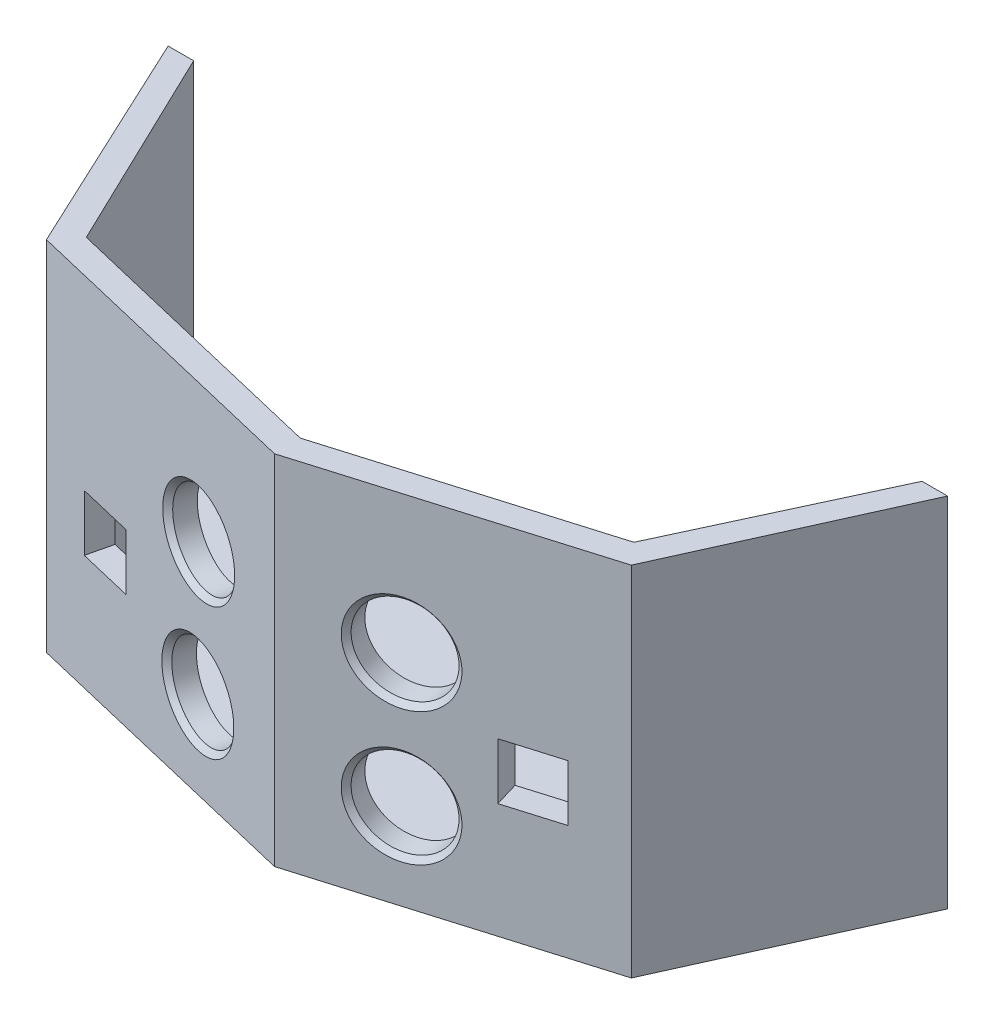
SolidWorks part; units mm, degrees
ref_plane "Front Plane" through (0, 0, 0) normal (0, 0, 1) x (1, 0, 0)
ref_plane "Top Plane" through (0, 0, 0) normal (0, 1, 0) x (1, 0, 0)
ref_plane "Right Plane" through (0, 0, 0) normal (1, 0, 0) x (0, 0, -1)
sketch "Sketch1" plane through (0, 0, 0) normal (0, 1, 0) x (1, 0, 0)
  line L15 (-55.374, -102.4826) -> (3.2527, -116.4495)
  line L16 (3.2527, -116.4495) -> (57.0602, -100.4088)
  line L19 (-55.374, -102.4826) -> (-76.3, -57.735)
  line L20 (57.0602, -100.4088) -> (76.3, -57.735)
  line L21 (-76.3, -57.735) -> (76.3, -57.735)
  line L23 (109.4621, -26.0776) -> (116.3881, 2.9946) [skipped]
  line L24 (-115.238, -7.3166) -> (-106.7, -35.9569) [skipped]
  line L25 (-103.4574, 51.2826) -> (-110.3834, 22.2104) [skipped]
  line L26 (96.1407, 63.9554) -> (74.4264, 84.4896) [skipped]
  line L27 (115.238, 7.3166) -> (98.162, 64.5972) [skipped]
  line L28 (26.0776, 109.4621) -> (-2.9946, 116.3881) [skipped]
  line L29 (-7.3166, 115.238) -> (-35.9569, 106.7) [skipped]
  line L30 (-63.9554, 96.1407) -> (-84.4896, 74.4264) [skipped]
  line L31 (-77.3149, -81.7581) -> (-55.6006, -102.2923) [skipped]
  line L32 (81.7581, -77.3149) -> (102.2923, -55.6006) [skipped]
  arc A1 (-59.5591, -93.5334) -> (60.4055, -92.9891) centre (0, 0) ccw construction
  dimension "D3" = 76.3
  dimension "D4" = 76.3
extrude "Boss-Extrude1" add sketch "Sketch1" along normal blind 70
sketch "Sketch4" plane through (0, 70, 0) normal (0, 1, 0) x (1, 0, 0)
  line L9 (-51.8673, -98.1781) -> (3.1082, -111.2752)
  line L10 (3.1082, -111.2752) -> (53.4415, -96.2702)
  line L13 (-55.374, -102.4826) -> (3.2527, -116.4495) construction
  line L14 (-51.8673, -98.1781) -> (-71.3, -57.735)
  line L16 (76.3, -57.735) -> (-76.3, -57.735) construction
  line L17 (53.4415, -96.2702) -> (71.3, -57.735)
  line L18 (-71.3, -57.735) -> (71.3, -57.735)
  line L19 (-76.3, -57.735) -> (-55.374, -102.4826) construction
  line L20 (-73.8794, -78.1253) -> (-53.1386, -97.7389) [skipped]
  line L21 (61.2536, -91.7207) -> (100.4809, -50.239) [skipped]
  line L22 (104.5982, -24.9188) -> (111.2137, 2.8501) [skipped]
  line L23 (-78.1253, 73.8794) -> (-97.7389, 53.1386) [skipped]
  line L24 (-110.0593, -7.1868) -> (-93.7487, -61.8995) [skipped]
  line L25 (-104.5982, 24.9188) -> (-111.2137, -2.8501) [skipped]
  line L26 (24.9188, 104.5982) -> (-2.8501, 111.2137) [skipped]
  line L27 (91.7207, 61.2536) -> (70.9799, 80.8672) [skipped]
  line L28 (103.0441, 30.7187) -> (94.8888, 58.0751) [skipped]
  line L29 (-30.7187, 103.0441) -> (-58.0751, 94.8888) [skipped]
  line L30 (57.0602, -100.4088) -> (76.3, -57.735) construction
  dimension "D1" = 5
  dimension "D2" = 5
  dimension "D3" = 5
  dimension "D4" = 5
  dimension "D5" = 5
extrude "Cut-Extrude1" cut sketch "Sketch4" against normal blind 65
sketch "Sketch5" plane through (-26.0776, 0, 109.4621) normal (-0.2317, 0, 0.9728) x (0.9728, 0, 0.2317)
  line L0 (-30.1163, 0) -> (30.1511, 0) construction
  line L1 (-10.0008, 51) -> (9.9992, 51) construction
  line L2 (-10.0008, 51) -> (-10.0008, 8) construction
  line L3 (-10.0008, 8) -> (9.9992, 8) construction
  line L4 (9.9992, 51) -> (9.9992, 8) construction
  line L6 (-30.1163, 70) -> (-30.1163, 0) construction
  circle A0 centre (10.1141, 42.999) radius 8.5
  circle A1 centre (9.8837, 17) radius 8.5
  dimension "D5" = 17
  dimension "D6" = 17
  dimension "D7" = 9
  dimension "D1" = 8
  dimension "D2" = 20
  dimension "D3" = 43
  dimension "D4" = 40
  dimension "D8" = 26
extrude "Cut-Extrude2" cut sketch "Sketch5" against normal blind 10
sketch "Sketch6" plane through (32.1472, 0, 107.8357) normal (0.2857, 0, 0.9583) x (0.9583, 0, -0.2857)
  line L1 (-20.1511, 51) -> (-0.1511, 51) construction
  line L2 (-20.1511, 51) -> (-20.1511, 8) construction
  line L3 (-20.1511, 8) -> (-0.1511, 8) construction
  line L4 (-0.1511, 51) -> (-0.1511, 8) construction
  line L6 (-30.1511, 70) -> (-30.1511, 0) construction
  line L7 (-30.1511, 0) -> (25.9965, 0) construction
  circle A0 centre (-10.1511, 17) radius 8.5
  circle A1 centre (-10.1511, 43) radius 8.5
  point P4 (5.1142, 27.5)
  dimension "D5" = 17
  dimension "D6" = 17
  dimension "D2" = 43
  dimension "D3" = 20
  dimension "D4" = 8
  dimension "D7" = 9
  dimension "D8" = 26
  dimension "D9" = 10
  dimension "D10" = 10
  dimension "D11" = 20
extrude "Cut-Extrude3" cut sketch "Sketch6" against normal blind 10
chamfer "Chamfer2" distance 1 angle 45 4 edges at (30.5649, 17, 108.3074) (30.5649, 43, 108.3074) (-8.1944, 17, 113.7224) (-7.9702, 42.999, 113.7759)
sketch "Sketch7" plane through (-26.0776, 0, 109.4621) normal (-0.2317, 0, 0.9728) x (0.9728, 0, 0.2317)
  line L0 (-30.1163, 0) -> (30.1511, 0) construction
  line L1 (-20.1163, 33.5) -> (-9.1163, 33.5)
  line L2 (-20.1163, 33.5) -> (-20.1163, 22.5)
  line L3 (-20.1163, 22.5) -> (-9.1163, 22.5)
  line L4 (-9.1163, 33.5) -> (-9.1163, 22.5)
  line L5 (-20.1163, 33.5) -> (-9.1163, 22.5) construction
  line L6 (-20.1163, 22.5) -> (-9.1163, 33.5) construction
  line L8 (-30.1163, 70) -> (-30.1163, 0) construction
  point P4 (-14.6163, 28)
  dimension "D1" = 11
  dimension "D2" = 28
  dimension "D3" = 10
extrude "Cut-Extrude4" cut sketch "Sketch7" against normal blind 10
sketch "Sketch8" plane through (32.1472, 0, 107.8357) normal (0.2857, 0, 0.9583) x (0.9583, 0, -0.2857)
  line L1 (4.9965, 33.5) -> (15.9965, 33.5)
  line L2 (4.9965, 33.5) -> (4.9965, 22.5)
  line L3 (4.9965, 22.5) -> (15.9965, 22.5)
  line L4 (15.9965, 33.5) -> (15.9965, 22.5)
  line L5 (4.9965, 33.5) -> (15.9965, 22.5) construction
  line L6 (4.9965, 22.5) -> (15.9965, 33.5) construction
  line L7 (-30.1511, 0) -> (25.9965, 0) construction
  line L9 (25.9965, 70) -> (25.9965, 0) construction
  point P4 (10.4965, 28)
  dimension "D1" = 11
  dimension "D2" = 11
  dimension "D3" = 10
  dimension "D4" = 28
extrude "Cut-Extrude5" cut sketch "Sketch8" against normal blind 10
sketch "Sketch9" plane through (0, 0, 57.735) normal (0, 0, -1) x (-1, 0, 0)
  line L0 (-3.1082, 5) -> (-53.4415, 5) construction
  line L1 (-7.5, 5) -> (7.5, 5)
  line L2 (-7.5, 5) -> (-7.5, 15)
  line L3 (-7.5, 15) -> (7.5, 15)
  line L4 (7.5, 5) -> (7.5, 15)
  line L5 (-7.5, 5) -> (7.5, 15) construction
  line L6 (-7.5, 15) -> (7.5, 5) construction
  point P4 (0, 10)
  point P11 (26.5, 10)
  dimension "D1" = 15
  dimension "D3" = 0
  dimension "D6" = 10
extrude "Boss-Extrude2" add sketch "Sketch9" against normal blind 6
fillet "Fillet1" radius 8 2 edges at (-7.5, 15, 60.735) (7.5, 15, 60.735)
fillet "Fillet2" radius 4 2 edges at (-7.5, 5, 60.735) (7.5, 5, 60.735)
sketch "Sketch11" plane through (0, 0, 57.735) normal (0, 0, -1) x (-1, 0, 0)
  line L1 (11.3322, 5) -> (71.3, 5) construction
  circle A0 centre (0, 9) radius 2.4849
  dimension "D1" = 4
  dimension "D2" = 0
extrude "Cut-Extrude7" cut sketch "Sketch11" against normal blind 10
